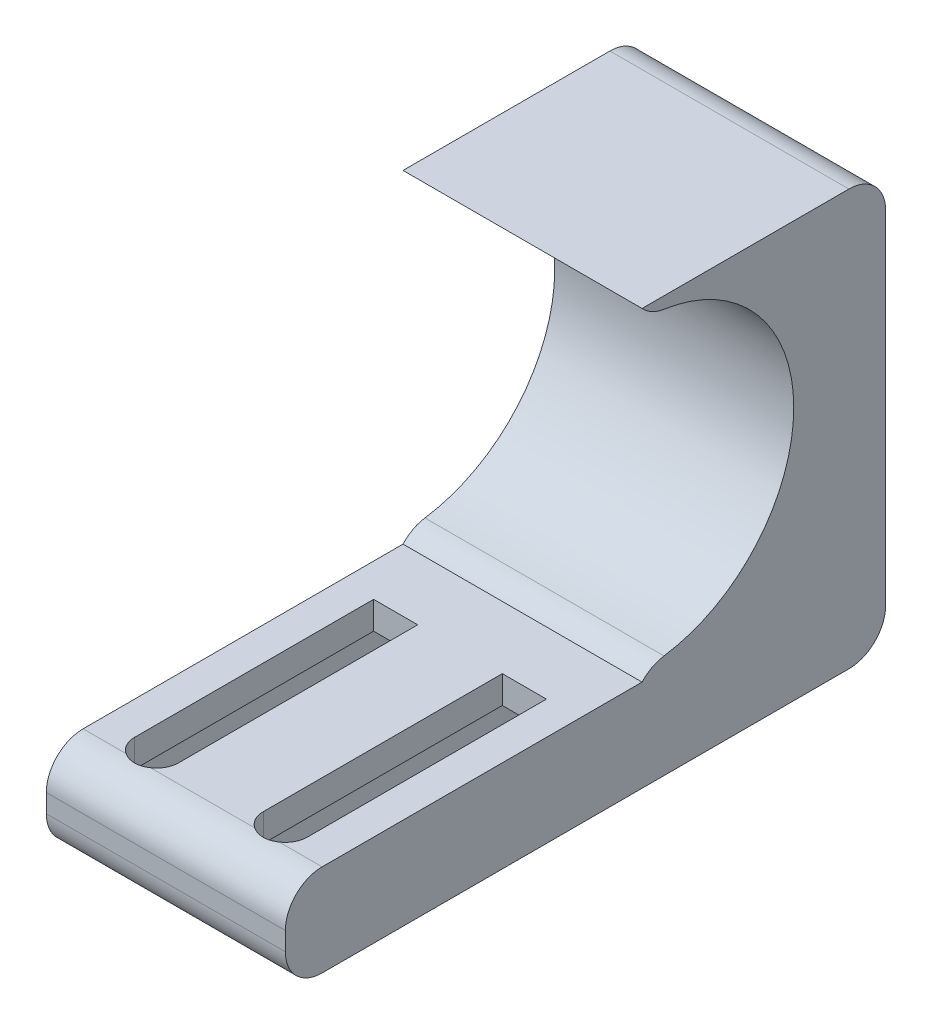
SolidWorks part; units mm, degrees
ref_plane "Front Plane" through (0, 0, 0) normal (0, 0, 1) x (1, 0, 0)
ref_plane "Top Plane" through (0, 0, 0) normal (0, 1, 0) x (1, 0, 0)
ref_plane "Right Plane" through (0, 0, 0) normal (1, 0, 0) x (0, 0, -1)
sketch "Sketch1" plane through (0, 0, 0) normal (0, 1, 0) x (1, 0, 0)
  line L0 (-6.5, -3.5) -> (6.5, -3.5) construction
  line L1 (-6.5, -6.5) -> (6.5, -6.5)
  line L2 (-6.5, -6.5) -> (-6.5, 6.5)
  line L3 (-6.5, 6.5) -> (6.5, 6.5)
  line L4 (6.5, -6.5) -> (6.5, 6.5)
  line L5 (-6.5, -6.5) -> (6.5, 6.5) construction
  line L6 (-6.5, 6.5) -> (6.5, -6.5) construction
  line L8 (-3.5, -1.7473) -> (-5.0179, -2.6237) construction
  line L9 (-5.0179, -2.6237) -> (-5.0179, -4.3763) construction
  line L10 (-5.0179, -4.3763) -> (-3.5, -5.2527) construction
  line L11 (-3.5, -5.2527) -> (-1.9821, -4.3763) construction
  line L12 (-1.9821, -4.3763) -> (-1.9821, -2.6237) construction
  line L13 (-1.9821, -2.6237) -> (-3.5, -1.7473) construction
  line L14 (3.5, -1.7473) -> (1.9821, -2.6237) construction
  line L15 (1.9821, -2.6237) -> (1.9821, -4.3763) construction
  line L16 (1.9821, -4.3763) -> (3.5, -5.2527) construction
  line L17 (3.5, -5.2527) -> (5.0179, -4.3763) construction
  line L18 (5.0179, -4.3763) -> (5.0179, -2.6237) construction
  line L19 (5.0179, -2.6237) -> (3.5, -1.7473) construction
  circle A0 centre (-3.5, -3.5) radius 1.5179 construction
  circle A1 centre (3.5, -3.5) radius 1.5179 construction
  point P0 (0, 0)
  dimension "D1" = 13
  dimension "D2" = 13
  dimension "D3" = 3
  dimension "D4" = 3
  dimension "D5" = 7
extrude "Boss-Extrude1" add sketch "Sketch1" along normal blind 5 contours L2 L3 L4 L1
sketch "Sketch2" plane through (0, 0, -6.5) normal (0, 0, -1) x (-1, 0, 0)
  line L1 (-6.5, 5) -> (6.5, 5)
  line L2 (-6.5, 5) -> (-6.5, 0)
  line L3 (-6.5, 0) -> (6.5, 0)
  line L4 (6.5, 5) -> (6.5, 0)
extrude "Boss-Extrude2" add sketch "Sketch2" along normal blind 16.4
sketch "Sketch3" plane through (0, 5, 0) normal (0, 1, 0) x (1, 0, 0)
  line L0 (6.5, -6.5) -> (6.5, 22.9) construction
  line L1 (-6.5, 22.9) -> (6.5, 22.9)
  line L2 (-6.5, 22.9) -> (-6.5, 12.9)
  line L3 (-6.5, 12.9) -> (6.5, 12.9)
  line L4 (6.5, 22.9) -> (6.5, 12.9)
  dimension "D1" = 10
extrude "Boss-Extrude3" add sketch "Sketch3" along normal blind 17.6
sketch "Sketch4" plane through (6.5, 0, 0) normal (1, 0, 0) x (0, 0, -1)
  line L0 (12.9, 22.6) -> (12.9, 5) construction
  circle A0 centre (12.9, 13.8) radius 8.25
  dimension "D1" = 16.5
extrude "Cut-Extrude1" cut sketch "Sketch4" against normal up to surface (13 mm away) up to face at (-6.5, 9.2, -9.7667)
sketch "Sketch5" plane through (0, 0, -22.9) normal (0, 0, -1) x (-1, 0, 0)
  line L1 (6.5, 0) -> (-6.5, 0)
  line L2 (6.5, 0) -> (6.5, 22.6)
  line L3 (6.5, 22.6) -> (-6.5, 22.6)
  line L4 (-6.5, 0) -> (-6.5, 22.6)
extrude "Boss-Extrude4" add sketch "Sketch5" along normal blind 3.25
ref_plane "Plane1" through (0, 2.5, 0) normal (0, 1, 0) x (1, 0, 0)
sketch "Sketch6" plane through (0, 0, 0) normal (0, -1, 0) x (1, 0, 0)
  line L0 (6.5, 3.5) -> (-6.5, 3.5) construction
  line L1 (6.5, 6.5) -> (6.5, -26.15) construction
  line L2 (-6.5, 6.5) -> (-6.5, -26.15) construction
  line L3 (-6.5, 6.5) -> (6.5, 6.5) construction
  line L4 (5.65, 2.2587) -> (5.65, -26.15)
  line L5 (3.5, 1.0174) -> (5.65, 2.2587) construction
  line L6 (5.65, 2.2587) -> (5.65, 4.7413)
  line L7 (5.65, 4.7413) -> (3.5, 5.9826)
  line L8 (3.5, 5.9826) -> (1.35, 4.7413)
  line L9 (1.35, 4.7413) -> (1.35, 2.2587)
  line L10 (1.35, 2.2587) -> (3.5, 1.0174) construction
  line L11 (-3.5, 1.0174) -> (-1.35, 2.2587) construction
  line L12 (-1.35, 2.2587) -> (-1.35, 4.7413)
  line L13 (-1.35, 4.7413) -> (-3.5, 5.9826)
  line L14 (-3.5, 5.9826) -> (-5.65, 4.7413)
  line L15 (-5.65, 4.7413) -> (-5.65, 2.2587)
  line L16 (-5.65, 2.2587) -> (-3.5, 1.0174) construction
  line L17 (6.5, -26.15) -> (-6.5, -26.15) construction
  line L18 (1.35, 2.2587) -> (1.35, -26.15)
  line L19 (-1.35, 2.2587) -> (-1.35, -26.15)
  line L20 (-5.65, 2.2587) -> (-5.65, -26.15)
  line L21 (5.65, -26.15) -> (1.35, -26.15)
  line L22 (-1.35, -26.15) -> (-5.65, -26.15)
  circle A0 centre (3.5, 3.5) radius 2.15 construction
  circle A1 centre (-3.5, 3.5) radius 2.15 construction
  dimension "D1" = 3
  dimension "D2" = 7
  dimension "D3" = 3
  dimension "D4" = 4.3
  dimension "D5" = 4.3
extrude "Cut-Extrude2" cut sketch "Sketch6" against normal blind 1 and the other way blind 1 from surface starting at plane "Plane1"
sketch "Sketch7" plane through (0, 0, 0) normal (0, -1, 0) x (1, 0, 0)
  line L0 (-2.3, 3.5) -> (-2.3, -9.5)
  line L2 (-4.7, 3.5) -> (-4.7, -9.5)
  line L3 (2.3, 3.5) -> (2.3, -9.5)
  line L5 (4.7, 3.5) -> (4.7, -9.5)
  line L6 (4.7, -9.5) -> (2.3, -9.5)
  line L7 (-2.3, -9.5) -> (-4.7, -9.5)
  line L8 (6.5, -9.5) -> (-6.5, -9.5) construction
  line L9 (6.5, 6.5) -> (6.5, -26.15) construction
  line L10 (-6.5, 6.5) -> (-6.5, -26.15) construction
  line L11 (-6.5, 6.5) -> (6.5, 6.5) construction
  arc A0 (-2.3, 3.5) -> (-4.7, 3.5) centre (-3.5, 3.5) ccw
  arc A1 (4.7, 3.5) -> (2.3, 3.5) centre (3.5, 3.5) ccw
  arc A2 (-4.7, 3.5) -> (-2.3, 3.5) centre (-3.5, 3.5) ccw construction
  arc A3 (2.3, 3.5) -> (4.7, 3.5) centre (3.5, 3.5) ccw construction
  dimension "D1" = 2.4
  dimension "D2" = 2.4
  dimension "D3" = 16
extrude "Cut-Extrude3" cut sketch "Sketch7" against normal up to surface (5 mm away) up to face at (0, 5, -3.2)
fillet "Fillet2" radius 2 6 edges at (0, 0, 6.5) (0, 5, 6.5) (0, 5.55, -12.9) (0, 22.05, -12.9) (0, 22.6, -26.15) (0, 0, -26.15)
equation "\"D5@Sketch6\"=\"D4@Sketch6\""
equation "\"D2@Sketch7\"=\"D1@Sketch7\""
